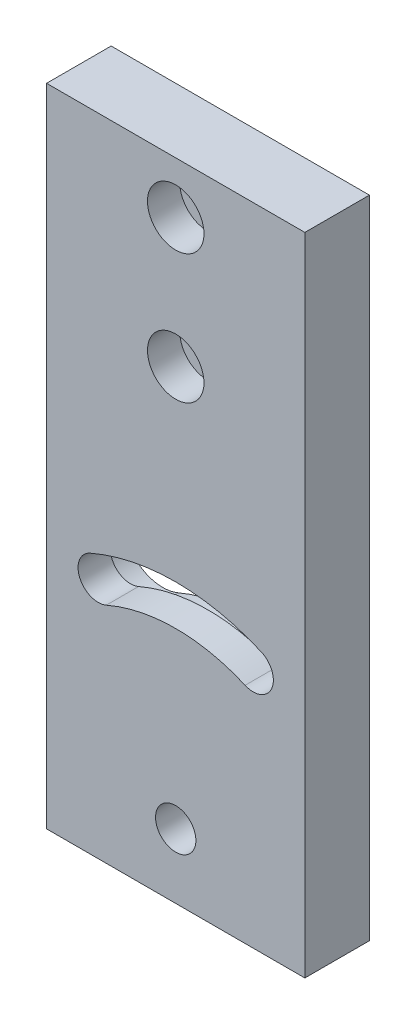
SolidWorks part; units mm, degrees
ref_plane "Front Plane" through (0, 0, 0) normal (0, 0, 1) x (1, 0, 0)
ref_plane "Top Plane" through (0, 0, 0) normal (0, 1, 0) x (1, 0, 0)
ref_plane "Right Plane" through (0, 0, 0) normal (1, 0, 0) x (0, 0, -1)
sketch "Sketch1" plane through (0, 0, 0) normal (0, 0, 1) x (1, 0, 0)
  line L1 (0, 0) -> (50.8, 0)
  line L2 (0, 0) -> (0, 127)
  line L3 (0, 127) -> (50.8, 127)
  line L4 (50.8, 0) -> (50.8, 127)
  circle A0 centre (25.4, 12.7) radius 3.9687
  circle A6 centre (25.4, 116.84) radius 3.3734
  circle A7 centre (25.4, 91.44) radius 3.3734
  arc A8 (42.2275, 51.2566) -> (8.5725, 51.2566) centre (25.4, 12.7) ccw
  arc A9 (39.0525, 43.9818) -> (11.7475, 43.9818) centre (25.4, 12.7) ccw
  arc A10 (8.5725, 51.2566) -> (11.7475, 43.9818) centre (10.16, 47.6192) ccw
  arc A11 (39.0525, 43.9818) -> (42.2275, 51.2566) centre (40.64, 47.6192) ccw
  arc A12 (43.7515, 54.7486) -> (7.0485, 54.7486) centre (25.4, 12.7) ccw
  arc A13 (7.0485, 54.7486) -> (13.2715, 40.4899) centre (10.16, 47.6192) ccw
  arc A14 (37.5285, 40.4899) -> (13.2715, 40.4899) centre (25.4, 12.7) ccw
  arc A15 (37.5285, 40.4899) -> (43.7515, 54.7486) centre (40.64, 47.6192) ccw
  dimension "D3" = 7.9375
  dimension "D6" = 6.7469
  dimension "D7" = 7.9375
  dimension "D8" = 7.9375
  dimension "D9" = 6.7469
  dimension "D13" = 84.1375
  dimension "D14" = 68.2625
  dimension "D1" = 127
  dimension "D2" = 50.8
  dimension "D4" = 25.4
  dimension "D5" = 12.7
  dimension "D10" = 10.16
  dimension "D11" = 10.16
  dimension "D12" = 25.4
  dimension "D15" = 10.16
  dimension "D17" = 25.4
  dimension "D18" = 0
  dimension "D16" = 3.81
extrude "Boss-Extrude2" add sketch "Sketch1" along normal blind 12.7 contours L2 L1 L4 L3 | A11 A8 A10 A9 | A7 | A6 | A0
extrude "Cut-Extrude1" cut sketch "Sketch1<3>" along normal blind 6.35 from surface contours A14 A15 A12 A13 A11 A9 A10 A8 region at (47.3138, 44.7065, 0) starting at face at (25.4, 48.4159, 0)
sketch "Sketch1<3>" plane through (0, 0, 0) normal (0, 0, 1) x (1, 0, 0) same geometry as "Sketch1"
sketch "Sketch3" plane through (0, 0, 0) normal (0, 0, -1) x (-1, 0, 0)
  circle A0 centre (-25.4, 116.84) radius 5.5562
  circle A1 centre (-25.4, 91.44) radius 5.5562
  dimension "D1" = 11.1125
  dimension "D2" = 11.1125
extrude "Cut-Extrude2" cut sketch "Sketch3" along normal blind 6.35 from surface starting at face at (28.7734, 116.84, 12.7)
sketch "Sketch4" plane through (0, 0, 12.7) normal (0, 0, 1) x (1, 0, 0)
  circle A0 centre (25.4, 12.7) radius 7.62
  dimension "D1" = 15.24
extrude "Cut-Extrude3" cut sketch "Sketch4" along normal blind 6.35 from surface starting at face at (25.4, 47.6539, 0)
